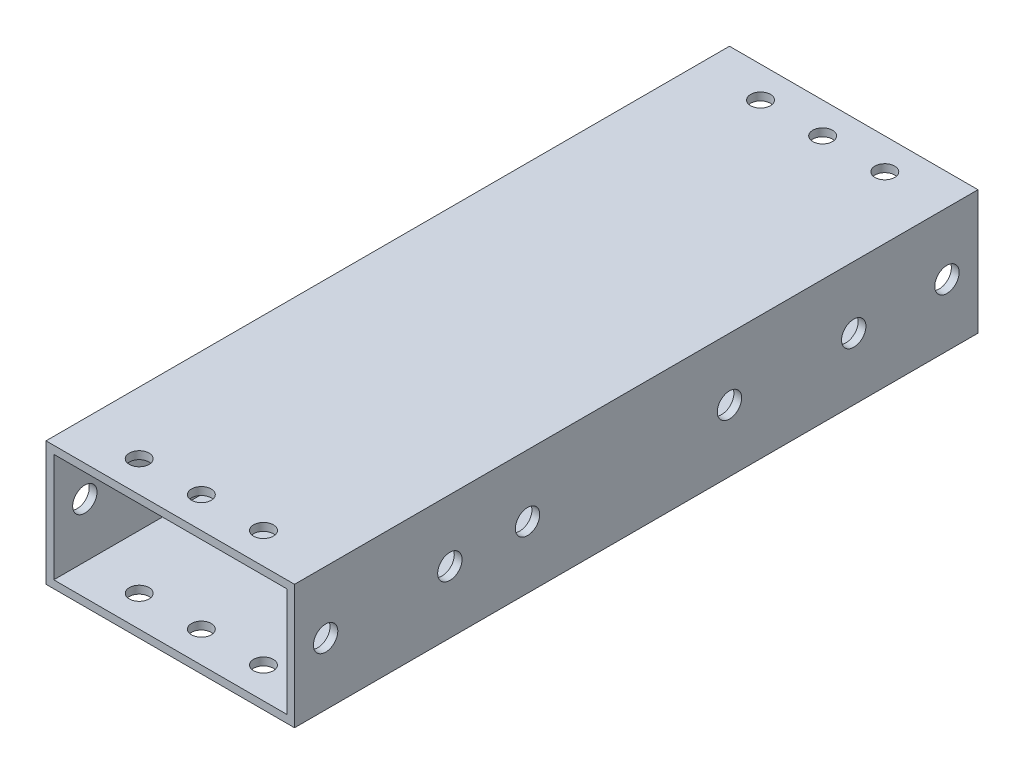
SolidWorks part; units mm, degrees
material "6061-T6 (SS)"
ref_plane "Front Plane" through (0, 0, 0) normal (0, 0, 1) x (1, 0, 0)
ref_plane "Top Plane" through (0, 0, 0) normal (0, 1, 0) x (1, 0, 0)
ref_plane "Right Plane" through (0, 0, 0) normal (1, 0, 0) x (0, 0, -1)
sketch "Sketch1" plane through (0, 0, 0) normal (0, 0, 1) x (1, 0, 0)
  line L0 (-23.8125, 11.1125) -> (23.8125, 11.1125)
  line L1 (-25.4, -12.7) -> (25.4, -12.7)
  line L2 (-25.4, -12.7) -> (-25.4, 12.7)
  line L3 (-25.4, 12.7) -> (25.4, 12.7)
  line L4 (25.4, -12.7) -> (25.4, 12.7)
  line L5 (-25.4, -12.7) -> (25.4, 12.7) construction
  line L6 (-25.4, 12.7) -> (25.4, -12.7) construction
  line L7 (23.8125, -11.1125) -> (23.8125, 11.1125)
  line L8 (-23.8125, -11.1125) -> (23.8125, -11.1125)
  line L9 (-23.8125, -11.1125) -> (-23.8125, 11.1125)
  point P0 (0, 0)
  dimension "D1" = 50.8
  dimension "D2" = 25.4
  dimension "D3" = 1.5875
extrude "Boss-Extrude1" add sketch "Sketch1" along normal mid plane 139.7
sketch "Sketch2" plane through (0, 12.7, 0) normal (0, 1, 0) x (1, 0, 0)
  line L0 (25.4, 69.85) -> (-25.4, 69.85) construction
  line L1 (25.4, 0) -> (-25.4, 0) construction
  line L2 (25.4, -69.85) -> (25.4, 69.85) construction
  line L3 (-25.4, -69.85) -> (-25.4, 69.85) construction
  circle A0 centre (-12.7, 63.5) radius 2.0193
  circle A1 centre (0, 63.5) radius 2.0193
  circle A2 centre (12.7, 63.5) radius 2.0193
  circle A3 centre (12.7, -63.5) radius 2.0193
  circle A4 centre (0, -63.5) radius 2.0193
  circle A5 centre (-12.7, -63.5) radius 2.0193
  dimension "D1" = 4.0386
  dimension "D2" = 12.7
  dimension "D3" = 12.7
  dimension "D4" = 6.35
extrude "Cut-Extrude1" cut sketch "Sketch2" against normal through all
sketch "Sketch3" plane through (25.4, 0, 0) normal (1, 0, 0) x (0, 0, -1)
  line L0 (0, 12.7) -> (0, -12.7) construction
  line L1 (-69.85, 12.7) -> (69.85, 12.7) construction
  line L2 (-69.85, -12.7) -> (69.85, -12.7) construction
  line L3 (-69.85, -12.7) -> (-69.85, 12.7) construction
  line L5 (69.85, -12.7) -> (69.85, 12.7) construction
  circle A8 centre (63.5, 0) radius 2.4892
  circle A9 centre (44.45, 0) radius 2.4892
  circle A10 centre (19.05, 0) radius 2.4892
  circle A11 centre (-63.5, 0) radius 2.4892
  circle A14 centre (-38.1, 0) radius 2.4892
  circle A15 centre (-22.225, 0) radius 2.4892
  dimension "D1" = 6.35
  dimension "D3" = 15.875
  dimension "D8" = 4.9784
  dimension "D2" = 31.75
  dimension "D4" = 25.4
  dimension "D7" = 25.4
extrude "Cut-Extrude2" cut sketch "Sketch3" against normal through all
